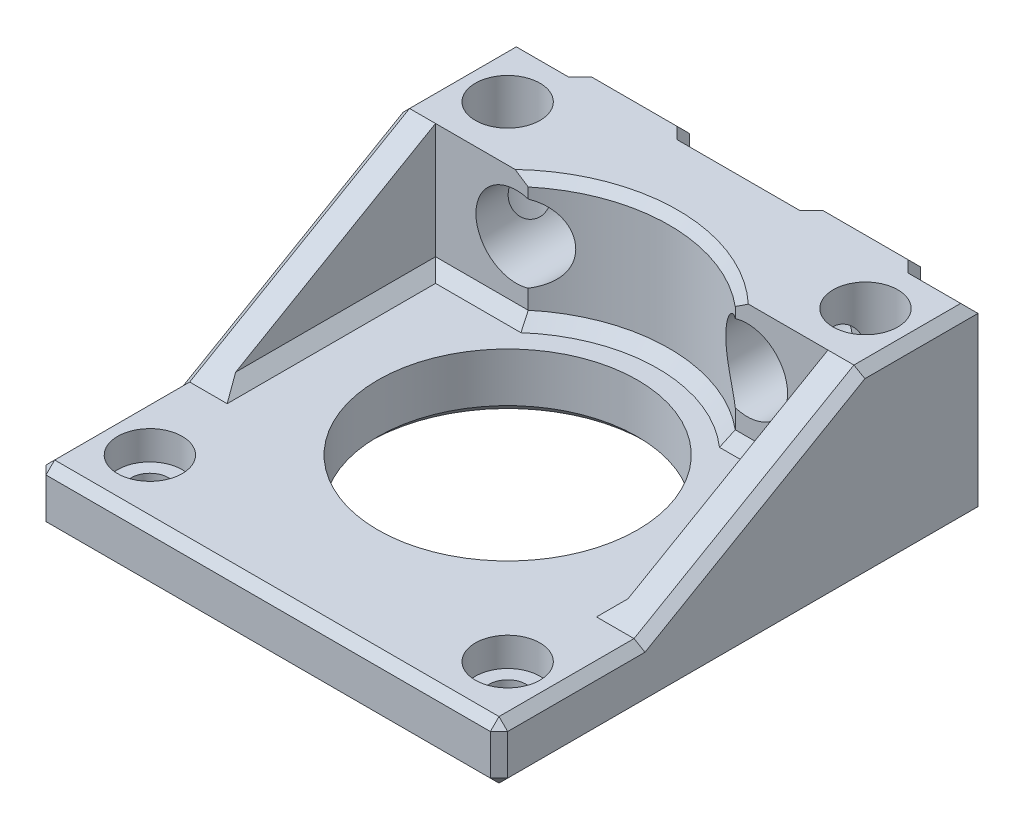
SolidWorks part; units mm, degrees
ref_plane "Front Plane" through (0, 0, 0) normal (0, 0, 1) x (1, 0, 0)
ref_plane "Top Plane" through (0, 0, 0) normal (0, 1, 0) x (1, 0, 0)
ref_plane "Right Plane" through (0, 0, 0) normal (1, 0, 0) x (0, 0, -1)
sketch "Sketch1" plane through (0, 0, 0) normal (0, 1, 0) x (1, 0, 0)
  line L0 (0, 0) -> (0, 11.25) construction
  line L1 (-20, 20.75) -> (-15, 20.75)
  line L2 (-20, 20.75) -> (-20, -20.75)
  line L3 (-20, -20.75) -> (20, -20.75)
  line L4 (20, 20.75) -> (20, -20.75)
  line L5 (0, 11.25) -> (0, 20.75) construction
  line L6 (-15, 20.75) -> (-14, 21.75)
  line L7 (-5, 20.75) -> (5, 20.75)
  line L8 (5, 20.75) -> (6, 21.75)
  line L9 (15, 20.75) -> (20, 20.75)
  line L10 (-14, 21.75) -> (-6, 21.75)
  line L11 (-6, 21.75) -> (-5, 20.75)
  line L12 (6, 21.75) -> (14, 21.75)
  line L13 (14, 21.75) -> (15, 20.75)
  line L14 (0, -20.75) -> (0, -11.25) construction
  line L15 (-15.5, -15.5) -> (15.5, -15.5) construction
  line L16 (-15.5, -15.5) -> (-15.5, 15.5) construction
  line L17 (-15.5, 15.5) -> (15.5, 15.5) construction
  line L18 (15.5, -15.5) -> (15.5, 15.5) construction
  line L19 (-15.5, -15.5) -> (15.5, 15.5) construction
  line L20 (-15.5, 15.5) -> (15.5, -15.5) construction
  circle A0 centre (0, 0) radius 11.25
  circle A1 centre (15.5, 15.5) radius 1.6
  circle A2 centre (-15.5, 15.5) radius 1.6
  circle A3 centre (-15.5, -15.5) radius 1.6
  circle A4 centre (15.5, -15.5) radius 1.6
  point P19 (0, 20.75)
  point P28 (0, 0)
  dimension "D1" = 22.5
  dimension "D10" = 3.2
  dimension "D2" = 9.5
  dimension "D3" = 40
  dimension "D5" = 30
  dimension "D6" = 10
  dimension "D7" = 1
  dimension "D9" = 31
  dimension "D4" = 135
extrude "Boss-Extrude1" add sketch "Sketch1" along normal blind 5
sketch "Sketch4" plane through (0, 5, 0) normal (0, 1, 0) x (1, 0, 0)
  circle A0 centre (-15.5, -15.5) radius 2.8
  circle A1 centre (15.5, 15.5) radius 2.8
  circle A2 centre (-15.5, 15.5) radius 2.8
  circle A3 centre (15.5, -15.5) radius 2.8
  circle A4 centre (15.5, -15.5) radius 1.6 construction
  circle A5 centre (-15.5, -15.5) radius 1.6 construction
  circle A6 centre (-15.5, 15.5) radius 1.6 construction
  circle A7 centre (15.5, 15.5) radius 1.6 construction
  dimension "D1" = 5.6
extrude "Cut-Extrude1" cut sketch "Sketch4" against normal offset from surface (2.5 mm away) 2.5 up to face at (0, 0, -14.1667)
sketch "Sketch2" plane through (0, 5, 0) normal (0, 1, 0) x (1, 0, 0)
  line L0 (0, 14) -> (0, 0) construction
  line L1 (-8.9687, 10.75) -> (-20, 10.75)
  line L2 (-20, 20.75) -> (-20, -20.75) construction
  line L3 (-20, 10.75) -> (-20, 20.75)
  line L5 (20, 20.75) -> (20, 10.75)
  line L6 (20, -20.75) -> (20, 20.75) construction
  line L7 (20, 10.75) -> (8.9687, 10.75)
  line L12 (-20, 20.75) -> (-15, 20.75)
  line L13 (-15, 20.75) -> (-14, 21.75)
  line L14 (-14, 21.75) -> (-6, 21.75)
  line L15 (-6, 21.75) -> (-5, 20.75)
  line L16 (-5, 20.75) -> (5, 20.75)
  line L17 (5, 20.75) -> (6, 21.75)
  line L18 (6, 21.75) -> (14, 21.75)
  line L19 (14, 21.75) -> (15, 20.75)
  line L20 (15, 20.75) -> (20, 20.75)
  arc A0 (-8.9687, 10.75) -> (8.9687, 10.75) centre (0, 0) cw
  circle A1 centre (-15.5, 15.5) radius 2.8
  circle A2 centre (15.5, 15.5) radius 2.8
  circle A5 centre (-15.5, 15.5) radius 2.8 construction
  circle A6 centre (15.5, 15.5) radius 2.8 construction
  line M3 (-20, 20.75) -> (-20, -20.75)
  line M5 (20, -20.75) -> (20, 20.75)
  line M6 (-15, 20.75) -> (-20, 20.75)
  line M8 (20, 20.75) -> (15, 20.75)
  line M9 (15, 20.75) -> (14, 21.75)
  line M10 (14, 21.75) -> (6, 21.75)
  line M11 (6, 21.75) -> (5, 20.75)
  line M12 (5, 20.75) -> (-5, 20.75)
  line M13 (-5, 20.75) -> (-6, 21.75)
  line M14 (-6, 21.75) -> (-14, 21.75)
  line M15 (-14, 21.75) -> (-15, 20.75)
  circle M44 centre (-15.5, 15.5) radius 2.8
  circle M45 centre (15.5, 15.5) radius 2.8
  dimension "D1" = 14
  dimension "D2" = 10
extrude "Boss-Extrude2" add sketch "Sketch2" along normal offset from surface (11 mm away) 16 contours L1 A0 L7 M5 M8 M9 M10 M11 M12 M13 M14 M15 M6 M3 M45 M44 region at (0, 5, -16.5343) up to face at (0, 0, -14.1667)
sketch "Sketch3" plane through (20, 0, 0) normal (1, 0, 0) x (0, 0, -1)
  line L0 (10.75, 16) -> (-8.3026, 5)
  line L1 (-20.75, 5) -> (10.75, 5) construction
  line L2 (-8.3026, 5) -> (10.75, 5)
  line L4 (10.75, 5) -> (10.75, 16)
  point P5 (10.75, 16)
  dimension "D1" = 60
extrude "Boss-Extrude3" add sketch "Sketch3" against normal blind 3
mirror "Mirror1" about plane through (0, 0, 0) normal (1, 0, 0) of "Boss-Extrude3"
chamfer "Chamfer2" distance 1 angle 45 5 edges at (17, 5, -1.2237) (12.9843, 5, -10.75) (0, 5, -14) (-12.9843, 5, -10.75) (-17, 5, -1.2237)
sketch "Sketch5" plane through (0, 0, -10.75) normal (0, 0, 1) x (1, 0, 0)
  line L0 (-10, 16) -> (-10, 11) construction
  line L2 (10, 11) -> (17, 11) construction
  line L3 (17, 6) -> (17, 16) construction
  line L4 (10, 11) -> (-10, 11) construction
  line L5 (-10, 11) -> (-17, 11) construction
  line L6 (-8.9687, 16) -> (-17, 16) construction
  line L7 (-17, 6) -> (-17, 16) construction
  line L8 (-10, 11) -> (-10, 5) construction
  line L9 (-8.5987, 5) -> (-16, 5) construction
  circle A0 centre (-10, 11) radius 2.1
  circle A1 centre (10, 11) radius 2.1
  point P2 (-10, 16)
  point P16 (-10, 16)
  dimension "D2" = 4.2
  dimension "D1" = 20
  dimension "D3" = 5
extrude "Cut-Extrude2" cut sketch "Sketch5" against normal up to next
sketch "Sketch6" plane through (0, 0, -10.75) normal (0, 0, 1) x (1, 0, 0)
  circle A0 centre (-10, 11) radius 3.5
  circle A1 centre (10, 11) radius 3.5
  arc A2 (-8.9687, 12.8293) -> (-8.9687, 9.1707) centre (-10, 11) ccw construction
  arc A3 (8.9687, 9.1707) -> (8.9687, 12.8293) centre (10, 11) ccw construction
  dimension "D1" = 7
extrude "Cut-Extrude3" cut sketch "Sketch6" against normal offset from surface (7 mm away) 3 up to face at (17.5, 8, -20.75)
chamfer "Chamfer3" distance 0.75 angle 45 36 edges at (15.5, 0, 17.1) (-15.5, 0, 17.1) (-15.5, 0, -13.9) (15.5, 0, -13.9) (0, 0, 11.25) (0, 0, 20.75) (20, 0, 0) (17.5, 0, -20.75) (14.5, 0, -21.25) (10, 0, -21.75) (5.5, 0, -21.25) (0, 0, -20.75) (-5.5, 0, -21.25) (-10, 0, -21.75) (-14.5, 0, -21.25) (-17.5, 0, -20.75) (-20, 0, 0) (20, 2.5, 20.75) (-20, 2.5, 20.75) (-20, 5, 14.5263) (-20, 10.5, -1.2237) (20, 10.5, -1.2237) (20, 5, 14.5263) (0, 5, 20.75) (0, 16, -14) (-17.5, 16, -20.75) (-14.5, 16, -21.25) (-10, 16, -21.75) (-5.5, 16, -21.25) (0, 16, -20.75) (5.5, 16, -21.25) (10, 16, -21.75) (14.5, 16, -21.25) (17.5, 16, -20.75) (20, 16, -15.75) (-20, 16, -15.75)
equation "\"Tolerance\"=0.2"
equation "\"D10@Sketch1\"=3 + \"Tolerance\""
equation "\"D1@Sketch4\"=5.4 + \"Tolerance\""
equation "\"D2@Sketch5\"=4 + \"Tolerance\""
equation "\"D1@Sketch6\"=6.8 + \"Tolerance\""
